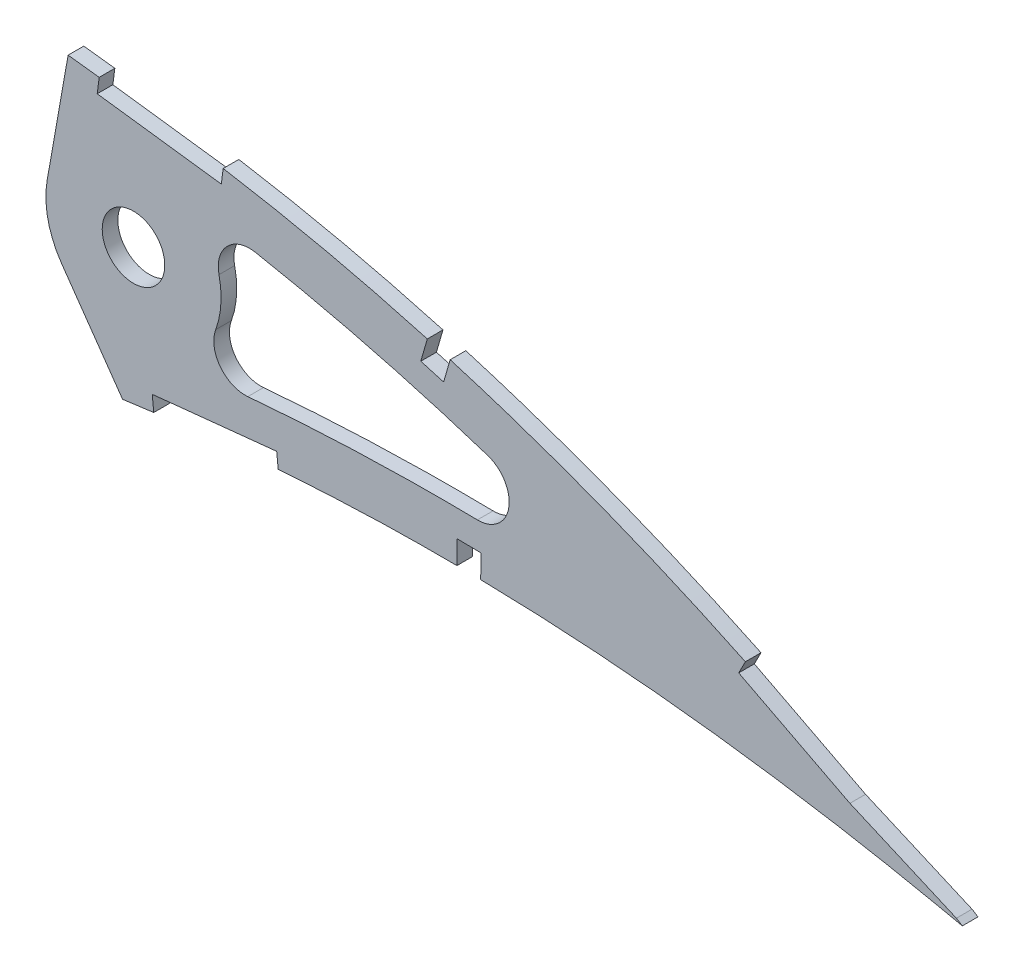
SolidWorks part; units mm, degrees
material "Plywood"
ref_plane "Front Plane" through (0, 0, 0) normal (0, 0, 1) x (1, 0, 0)
ref_plane "Top Plane" through (0, 0, 0) normal (0, 1, 0) x (1, 0, 0)
ref_plane "Right Plane" through (0, 0, 0) normal (1, 0, 0) x (0, 0, -1)
curve "Curve1"
  spline degree 3 poles (554.3197, 0.8642, 0) (554.2772, 0.8904, 0) (554.1075, 0.9953, 0) (553.7252, 1.2298, 0) (553.0885, 1.6204, 0) (552.1972, 2.1644, 0) (551.0519, 2.8603, 0) (549.6522, 3.7033, 0) (547.9988, 4.6906, 0) (546.0922, 5.8176, 0) (543.9326, 7.0789, 0) (541.5207, 8.4695, 0) (538.8569, 9.9815, 0) (535.942, 11.6087, 0) (532.7772, 13.3434, 0) (529.3631, 15.1777, 0) (525.7007, 17.1023, 0) (521.7917, 19.109, 0) (517.6366, 21.1866, 0) (513.2374, 23.3265, 0) (508.5956, 25.518, 0) (503.7128, 27.7495, 0) (498.5918, 30.0118, 0) (493.234, 32.2909, 0) (487.6424, 34.577, 0) (481.8195, 36.8569, 0) (475.7686, 39.1203, 0) (469.4922, 41.3526, 0) (462.9949, 43.5439, 0) (456.2798, 45.6802, 0) (449.3518, 47.7496, 0) (442.2149, 49.739, 0) (434.875, 51.6379, 0) (427.3368, 53.4327, 0) (419.6066, 55.1112, 0) (411.6907, 56.6635, 0) (403.5957, 58.0739, 0) (395.344, 59.3415, 0) (387.0683, 60.3958, 0) (378.8096, 61.4299, 0) (370.5633, 62.4014, 0) (362.2161, 63.3317, 0) (353.7762, 64.2156, 0) (345.252, 65.0503, 0) (336.6519, 65.8323, 0) (327.9851, 66.5592, 0) (319.2598, 67.227, 0) (310.4852, 67.8346, 0) (301.6702, 68.3766, 0) (292.8239, 68.8527, 0) (283.9555, 69.2595, 0) (275.0741, 69.5943, 0) (266.1892, 69.8549, 0) (257.3099, 70.039, 0) (248.446, 70.1454, 0) (239.6066, 70.171, 0) (230.8014, 70.1156, 0) (222.0395, 69.9772, 0) (213.3305, 69.7538, 0) (204.6838, 69.4452, 0) (196.1087, 69.0513, 0) (187.6145, 68.5689, 0) (179.2105, 68.0012, 0) (170.9059, 67.3456, 0) (162.7101, 66.6021, 0) (154.6315, 65.7736, 0) (146.6791, 64.8581, 0) (138.8614, 63.858, 0) (131.1871, 62.7754, 0) (123.6647, 61.6096, 0) (116.3022, 60.3641, 0) (109.1077, 59.04, 0) (102.0887, 57.6413, 0) (95.2529, 56.1683, 0) (88.6074, 54.6255, 0) (82.1593, 53.0155, 0) (75.9155, 51.3413, 0) (69.8822, 49.607, 0) (64.0656, 47.8163, 0) (58.4725, 45.9714, 0) (53.107, 44.0792, 0) (47.9758, 42.141, 0) (43.0829, 40.1629, 0) (38.4338, 38.1474, 0) (34.0322, 36.1008, 0) (29.883, 34.0255, 0) (25.9891, 31.9271, 0) (22.3545, 29.809, 0) (18.9827, 27.675, 0) (15.875, 25.5306, 0) (13.0358, 23.3771, 0) (10.4661, 21.22, 0) (8.1674, 19.0625, 0) (6.143, 16.9061, 0) (4.3929, 14.7547, 0) (2.9194, 12.6099, 0) (1.7228, 10.4738, 0) (0.8056, 8.3479, 0) (0.1671, 6.2334, 0) (-0.1824, 4.1334, 0) (-0.2694, 2.0463, 0) (-0.0897, 0.6811, 0) (0, 0, 0) knots 0 0 0 0 0.000254 0.001015 0.002283 0.004057 0.006331 0.009105 0.012374 0.016134 0.02038 0.025106 0.030306 0.035972 0.0421 0.048678 0.055702 0.06316 0.071046 0.07935 0.088063 0.097176 0.106678 0.116562 0.126814 0.137428 0.148394 0.1597 0.171338 0.183298 0.19557 0.208144 0.221012 0.234162 0.247587 0.261277 0.275223 0.289414 0.303771 0.317689 0.331784 0.34604 0.360444 0.374983 0.38964 0.404403 0.419257 0.434187 0.449177 0.464215 0.479284 0.49437 0.509458 0.524532 0.539579 0.554583 0.56953 0.584403 0.599191 0.613877 0.628447 0.642889 0.657186 0.671326 0.685294 0.699078 0.712665 0.726043 0.739198 0.752118 0.764792 0.777208 0.789356 0.801224 0.812804 0.824083 0.835055 0.84571 0.856038 0.866034 0.875689 0.884998 0.893953 0.902553 0.910789 0.918661 0.926166 0.933303 0.940071 0.946475 0.952518 0.958205 0.963547 0.968557 0.97325 0.977651 0.981787 0.985694 0.989415 0.993001 0.996508 1 1 1 1
curve "Curve2"
  spline degree 3 poles (0, 0, 0) (0.1423, -0.672, 0) (0.4277, -2.019, 0) (1.203, -3.9582, 0) (2.2282, -5.8223, 0) (3.5249, -7.6064, 0) (5.0845, -9.31, 0) (6.9036, -10.9348, 0) (8.9803, -12.4801, 0) (11.3119, -13.945, 0) (13.8951, -15.3312, 0) (16.7269, -16.6378, 0) (19.8048, -17.8643, 0) (23.1254, -19.0092, 0) (26.6846, -20.0741, 0) (30.4791, -21.0566, 0) (34.5045, -21.9578, 0) (38.7571, -22.7757, 0) (43.232, -23.5109, 0) (47.9248, -24.1631, 0) (52.8305, -24.7327, 0) (57.9444, -25.2185, 0) (63.2614, -25.6215, 0) (68.7762, -25.942, 0) (74.4834, -26.1811, 0) (80.3777, -26.3377, 0) (86.4531, -26.4144, 0) (92.7043, -26.4123, 0) (99.1251, -26.3308, 0) (105.71, -26.1745, 0) (112.4527, -25.9423, 0) (119.3471, -25.6371, 0) (126.387, -25.2619, 0) (133.5661, -24.818, 0) (140.8781, -24.3074, 0) (148.3166, -23.7341, 0) (155.8748, -23.0997, 0) (163.5462, -22.4077, 0) (171.324, -21.6617, 0) (179.2015, -20.864, 0) (187.1716, -20.0183, 0) (195.2274, -19.1275, 0) (203.3619, -18.1963, 0) (211.5677, -17.2262, 0) (219.8379, -16.223, 0) (228.1647, -15.1885, 0) (236.5412, -14.1266, 0) (244.9597, -13.0425, 0) (253.4125, -11.9359, 0) (261.8924, -10.8148, 0) (270.3912, -9.6781, 0) (278.9016, -8.5319, 0) (287.4156, -7.3796, 0) (295.925, -6.2216, 0) (304.4222, -5.0626, 0) (312.8995, -3.9059, 0) (321.3485, -2.7516, 0) (329.7616, -1.6054, 0) (338.1302, -0.4672, 0) (346.4467, 0.6607, 0) (354.7031, 1.775, 0) (362.8916, 2.8743, 0) (371.0037, 3.9578, 0) (379.0314, 5.0259, 0) (386.8463, 6.0463, 0) (394.4281, 7.0733, 0) (401.8022, 7.9152, 0) (409.0845, 8.6338, 0) (416.2825, 9.2229, 0) (423.3877, 9.6911, 0) (430.3918, 10.0417, 0) (437.2865, 10.2795, 0) (444.0631, 10.4116, 0) (450.7132, 10.4414, 0) (457.2276, 10.3785, 0) (463.598, 10.2277, 0) (469.8153, 9.9961, 0) (475.8709, 9.6912, 0) (481.7563, 9.3216, 0) (487.4626, 8.8925, 0) (492.9818, 8.4141, 0) (498.3055, 7.8933, 0) (503.4254, 7.336, 0) (508.334, 6.7541, 0) (513.0236, 6.1512, 0) (517.4871, 5.5374, 0) (521.7172, 4.9187, 0) (525.7074, 4.3032, 0) (529.4512, 3.6966, 0) (532.9427, 3.1071, 0) (536.1764, 2.5402, 0) (539.1467, 2.0013, 0) (541.8495, 1.4973, 0) (544.2794, 1.0307, 0) (546.4331, 0.6092, 0) (548.3068, 0.2346, 0) (549.8976, -0.0878, 0) (551.2027, -0.3567, 0) (552.2202, -0.5677, 0) (552.948, -0.7211, 0) (553.3854, -0.8124, 0) (553.5798, -0.8538, 0) (553.6283, -0.8642, 0) knots 0 0 0 0 0.003638 0.007293 0.011028 0.014901 0.018963 0.023258 0.027821 0.032679 0.037853 0.043362 0.049215 0.055422 0.061989 0.068918 0.076211 0.083868 0.091887 0.100266 0.109 0.118085 0.127515 0.137285 0.147388 0.157816 0.168563 0.179619 0.190977 0.202627 0.21456 0.226767 0.239236 0.251959 0.264924 0.27812 0.291536 0.30516 0.318981 0.332985 0.347163 0.361499 0.375981 0.390597 0.405333 0.420175 0.43511 0.450124 0.465203 0.480333 0.495501 0.51069 0.525887 0.541078 0.556247 0.571382 0.586466 0.601485 0.616424 0.631269 0.646007 0.660621 0.675098 0.689423 0.703582 0.716908 0.730009 0.742952 0.755726 0.76832 0.780724 0.792927 0.804916 0.816679 0.828204 0.839475 0.850481 0.861208 0.871639 0.881763 0.891564 0.901027 0.910139 0.918884 0.927249 0.935221 0.942785 0.949928 0.956638 0.962904 0.968712 0.974054 0.978918 0.983297 0.98718 0.990561 0.993433 0.995791 0.99763 0.998946 0.999737 1 1 1 1
sketch "Sketch1" plane through (0, 0, 0) normal (0, 0, 1) x (1, 0, 0)
  line L28 (0, 63.5) -> (-23.1981, 63.5) construction
  line L39 (379.9183, -27.3345) -> (379.9183, 27.3345) construction
  line L40 (368.4067, 59.4277) -> (353.2793, 2.9714) construction
  line L41 (537.5238, 0.838) -> (542.0214, -1.9404)
  line L42 (536.8534, -0.838) -> (542.0214, -1.9404)
  circle A0 centre (68.58, 6.35) radius 9.525 construction
  circle A1 centre (246.38, 6.35) radius 9.525 construction
  spline S3 degree 3 poles (0, 0) (0.138, -0.6516) (0.4147, -1.9578) (1.1665, -3.8383) (2.1607, -5.6459) (3.4181, -7.3759) (4.9305, -9.0279) (6.6944, -10.6035) (8.7082, -12.1019) (10.9692, -13.5225) (13.4741, -14.8667) (16.2201, -16.1336) (19.2047, -17.323) (22.4247, -18.4332) (25.8761, -19.4659) (29.5556, -20.4185) (33.4591, -21.2925) (37.5827, -22.0856) (41.9221, -22.7985) (46.4726, -23.431) (51.2297, -23.9833) (56.1887, -24.4544) (61.3446, -24.8452) (66.6923, -25.156) (72.2266, -25.3878) (77.9422, -25.5397) (83.8336, -25.6141) (89.8954, -25.612) (96.1216, -25.533) (102.507, -25.3814) (109.0454, -25.1563) (115.7309, -24.8603) (122.5575, -24.4965) (129.5191, -24.066) (136.6095, -23.5709) (143.8226, -23.015) (151.1518, -22.3997) (158.5908, -21.7287) (166.1329, -21.0053) (173.7717, -20.2318) (181.5003, -19.4118) (189.312, -18.5479) (197.2, -17.6449) (205.1572, -16.7043) (213.1768, -15.7315) (221.2513, -14.7283) (229.374, -13.6986) (237.5374, -12.6473) (245.7341, -11.5743) (253.957, -10.4871) (262.1983, -9.3849) (270.4508, -8.2734) (278.7069, -7.156) (286.9584, -6.033) (295.1983, -4.9092) (303.4187, -3.7876) (311.6117, -2.6683) (319.7698, -1.5568) (327.8848, -0.4531) (335.9493, 0.6407) (343.9556, 1.7212) (351.896, 2.7872) (359.7623, 3.8379) (367.5468, 4.8736) (375.1249, 5.8631) (382.4769, 6.859) (389.6276, 7.6754) (396.6892, 8.3722) (403.6691, 8.9435) (410.559, 9.3975) (417.3509, 9.7374) (424.0367, 9.968) (430.608, 10.0961) (437.0566, 10.1251) (443.3736, 10.064) (449.5509, 9.9178) (455.5799, 9.6932) (461.4521, 9.3976) (467.1591, 9.0391) (472.6925, 8.6231) (478.0445, 8.1591) (483.2068, 7.6541) (488.1716, 7.1138) (492.9315, 6.5494) (497.479, 5.9648) (501.8072, 5.3696) (505.9092, 4.7697) (509.7784, 4.1728) (513.4088, 3.5846) (516.7946, 3.013) (519.9303, 2.4632) (522.8106, 1.9407) (525.4315, 1.4519) (527.7877, 0.9995) (529.8762, 0.5907) (531.6931, 0.2275) (533.2357, -0.0851) (534.5012, -0.3459) (535.4879, -0.5505) (536.1937, -0.6992) (536.6178, -0.7878) (536.8063, -0.828) (536.8534, -0.838) knots 0 0 0 0 0.003638 0.007293 0.011028 0.014901 0.018963 0.023258 0.027821 0.032679 0.037853 0.043362 0.049215 0.055422 0.061989 0.068918 0.076211 0.083868 0.091887 0.100266 0.109 0.118085 0.127515 0.137285 0.147388 0.157816 0.168563 0.179619 0.190977 0.202627 0.21456 0.226767 0.239236 0.251959 0.264924 0.27812 0.291536 0.30516 0.318981 0.332985 0.347163 0.361499 0.375981 0.390597 0.405333 0.420175 0.43511 0.450124 0.465203 0.480333 0.495501 0.51069 0.525887 0.541078 0.556247 0.571382 0.586466 0.601485 0.616424 0.631269 0.646007 0.660621 0.675098 0.689423 0.703582 0.716908 0.730009 0.742952 0.755726 0.76832 0.780724 0.792927 0.804916 0.816679 0.828204 0.839475 0.850481 0.861208 0.871639 0.881763 0.891564 0.901027 0.910139 0.918884 0.927249 0.935221 0.942785 0.949928 0.956638 0.962904 0.968712 0.974054 0.978918 0.983297 0.98718 0.990561 0.993433 0.995791 0.99763 0.998946 0.999737 1 1 1 1
  spline S6 degree 3 poles (537.5238, 0.838) (537.4826, 0.8635) (537.3181, 0.9651) (536.9473, 1.1925) (536.3299, 1.5713) (535.4656, 2.0988) (534.3551, 2.7737) (532.9977, 3.5911) (531.3944, 4.5485) (529.5456, 5.6413) (527.4514, 6.8644) (525.1126, 8.2129) (522.5295, 9.6791) (519.703, 11.2569) (516.6341, 12.9391) (513.3234, 14.7178) (509.772, 16.5841) (505.9814, 18.53) (501.9522, 20.5446) (497.6863, 22.6197) (493.1852, 24.7448) (488.4503, 26.9087) (483.4845, 29.1025) (478.289, 31.3125) (472.8669, 33.5293) (467.2204, 35.7401) (461.3528, 37.9349) (455.2666, 40.0996) (448.9661, 42.2246) (442.4545, 44.296) (435.7364, 46.3028) (428.8157, 48.2319) (421.6983, 50.0733) (414.3885, 51.8137) (406.8926, 53.4414) (399.2165, 54.9466) (391.3668, 56.3143) (383.365, 57.5434) (375.3401, 58.5658) (367.3317, 59.5686) (359.3352, 60.5106) (351.241, 61.4127) (343.0568, 62.2698) (334.7908, 63.0793) (326.4514, 63.8376) (318.0471, 64.5425) (309.5862, 65.19) (301.0775, 65.7792) (292.5296, 66.3048) (283.9513, 66.7665) (275.3516, 67.161) (266.7393, 67.4856) (258.1236, 67.7383) (249.5134, 67.9168) (240.9181, 68.0199) (232.3465, 68.0449) (223.8081, 67.9911) (215.3117, 67.8569) (206.8666, 67.6403) (198.4819, 67.341) (190.1666, 66.959) (181.9298, 66.4913) (173.7804, 65.9407) (165.7275, 65.305) (157.78, 64.584) (149.9461, 63.7807) (142.2347, 62.8929) (134.6539, 61.9231) (127.2121, 60.8733) (119.9176, 59.7429) (112.7783, 58.535) (105.8017, 57.2511) (98.9954, 55.8947) (92.3667, 54.4664) (85.9226, 52.9703) (79.6699, 51.4091) (73.6153, 49.7857) (67.7648, 48.1039) (62.1244, 46.3675) (56.7008, 44.5785) (51.4979, 42.7436) (46.5222, 40.8641) (41.7775, 38.9459) (37.2693, 36.9916) (33.0011, 35.007) (28.9776, 32.9945) (25.2017, 30.9597) (21.6772, 28.9058) (18.4075, 26.8364) (15.394, 24.757) (12.6408, 22.6688) (10.1489, 20.577) (7.9199, 18.4849) (5.9569, 16.3939) (4.2598, 14.3076) (2.831, 12.2278) (1.6706, 10.1565) (0.7812, 8.095) (0.162, 6.0445) (-0.1769, 4.0082) (-0.2612, 1.9843) (-0.087, 0.6604) (0, 0) knots 0 0 0 0 0.000254 0.001015 0.002283 0.004057 0.006331 0.009105 0.012374 0.016134 0.02038 0.025106 0.030306 0.035972 0.0421 0.048678 0.055702 0.06316 0.071046 0.07935 0.088063 0.097176 0.106678 0.116562 0.126814 0.137428 0.148394 0.1597 0.171338 0.183298 0.19557 0.208144 0.221012 0.234162 0.247587 0.261277 0.275223 0.289414 0.303771 0.317689 0.331784 0.34604 0.360444 0.374983 0.38964 0.404403 0.419257 0.434187 0.449177 0.464215 0.479284 0.49437 0.509458 0.524532 0.539579 0.554583 0.56953 0.584403 0.599191 0.613877 0.628447 0.642889 0.657186 0.671326 0.685294 0.699078 0.712665 0.726043 0.739198 0.752118 0.764792 0.777208 0.789356 0.801224 0.812804 0.824083 0.835055 0.84571 0.856038 0.866034 0.875689 0.884998 0.893953 0.902553 0.910789 0.918661 0.926166 0.933303 0.940071 0.946475 0.952518 0.958205 0.963547 0.968557 0.97325 0.977651 0.981787 0.985694 0.989415 0.993001 0.996508 1 1 1 1
  point P10 (78.5929, 16.5948)
  point P11 (227.8303, 32.4941)
  dimension "D2" = 19.05
  dimension "D18" = 177.8
  dimension "D3" = 15
  dimension "D5" = 63.5
  dimension "D7" = 57.15
  dimension "D12" = 57.15
  dimension "D17" = 68.58
extrude "Boss-Extrude1" add sketch "Sketch1" along normal blind 3.175
sketch "Sketch4" plane through (0, 0, 0) normal (0, 0, -1) x (-1, 0, 0)
  line L0 (-356.287, 36.32) -> (-360.5267, 60.365)
  line L1 (-359.2323, 23.0344) -> (-371.5795, 5.4008)
  line L2 (-373.7968, 33.2326) -> (-412.6852, 33.2326)
  circle A0 centre (-373.7968, 33.2326) radius 17.78
  circle A1 centre (-373.7968, 33.2326) radius 6.35
  spline S0 degree 3 poles (-1632.0302, 1674.0962) (-565.4284, -22.6918) (-552.7247, -8.4851) (-536.9473, 1.1925) (-536.3299, 1.5713) (-535.4656, 2.0988) (-534.3551, 2.7737) (-532.9977, 3.5911) (-531.3944, 4.5485) (-529.5456, 5.6413) (-527.4514, 6.8644) (-525.1126, 8.2129) (-522.5295, 9.6791) (-519.703, 11.2569) (-516.6341, 12.9391) (-513.3234, 14.7178) (-509.772, 16.5841) (-505.9814, 18.53) (-501.9522, 20.5446) (-497.6863, 22.6197) (-493.1852, 24.7448) (-488.4503, 26.9087) (-483.4845, 29.1025) (-478.289, 31.3125) (-472.8669, 33.5293) (-467.2204, 35.7401) (-461.3528, 37.9349) (-455.2666, 40.0996) (-448.9661, 42.2246) (-442.4545, 44.296) (-435.7364, 46.3028) (-428.8157, 48.2319) (-421.6983, 50.0733) (-414.3885, 51.8137) (-406.8926, 53.4414) (-399.2165, 54.9466) (-391.3668, 56.3143) (-383.365, 57.5434) (-375.3401, 58.5658) (-367.3317, 59.5686) (-359.3352, 60.5106) (-351.241, 61.4127) (-343.0568, 62.2698) (-334.7908, 63.0793) (-326.4514, 63.8376) (-318.0471, 64.5425) (-309.5862, 65.19) (-301.0775, 65.7792) (-292.5296, 66.3048) (-283.9513, 66.7665) (-275.3516, 67.161) (-266.7393, 67.4856) (-258.1236, 67.7383) (-249.5134, 67.9168) (-240.9181, 68.0199) (-232.3465, 68.0449) (-223.8081, 67.9911) (-215.3117, 67.8569) (-206.8666, 67.6403) (-198.4819, 67.341) (-190.1666, 66.959) (-181.9298, 66.4913) (-173.7804, 65.9407) (-165.7275, 65.305) (-157.78, 64.584) (-149.9461, 63.7807) (-142.2347, 62.8929) (-134.6539, 61.9231) (-127.2121, 60.8733) (-119.9176, 59.7429) (-112.7783, 58.535) (-105.8017, 57.2511) (-98.9954, 55.8947) (-92.3667, 54.4664) (-85.9226, 52.9703) (-79.6699, 51.4091) (-73.6153, 49.7857) (-67.7648, 48.1039) (-62.1244, 46.3675) (-56.7008, 44.5785) (-51.4979, 42.7436) (-46.5222, 40.8641) (-41.7775, 38.9459) (-37.2693, 36.9916) (-33.0011, 35.007) (-28.9776, 32.9945) (-25.2017, 30.9597) (-21.6772, 28.9058) (-18.4075, 26.8364) (-15.394, 24.757) (-12.6408, 22.6688) (-10.1489, 20.577) (-7.9199, 18.4849) (-5.9569, 16.3939) (-4.2598, 14.3076) (-2.831, 12.2278) (-1.6706, 10.1565) (-0.7812, 8.095) (-0.162, 6.0445) (0.1769, 4.0082) (1.1707, -19.8347) (-66.7598, -38.6935) (1990.434, -189.4699) knots -0.094882 -0.094882 -0.094882 -0.094882 0.000254 0.001015 0.002283 0.004057 0.006331 0.009105 0.012374 0.016134 0.02038 0.025106 0.030306 0.035972 0.0421 0.048678 0.055702 0.06316 0.071046 0.07935 0.088063 0.097176 0.106678 0.116562 0.126814 0.137428 0.148394 0.1597 0.171338 0.183298 0.19557 0.208144 0.221012 0.234162 0.247587 0.261277 0.275223 0.289414 0.303771 0.317689 0.331784 0.34604 0.360444 0.374983 0.38964 0.404403 0.419257 0.434187 0.449177 0.464215 0.479284 0.49437 0.509458 0.524532 0.539579 0.554583 0.56953 0.584403 0.599191 0.613877 0.628447 0.642889 0.657186 0.671326 0.685294 0.699078 0.712665 0.726043 0.739198 0.752118 0.764792 0.777208 0.789356 0.801224 0.812804 0.824083 0.835055 0.84571 0.856038 0.866034 0.875689 0.884998 0.893953 0.902553 0.910789 0.918661 0.926166 0.933303 0.940071 0.946475 0.952518 0.958205 0.963547 0.968557 0.97325 0.977651 0.981787 0.985694 0.989415 0.993001 0.996508 1.114113 1.114113 1.114113 1.114113 only from (-537.5238, 0.838) to (0, 0) construction
  spline S1 degree 3 poles (1940.1203, -483.4322) (-49.9299, 58.7424) (7.7069, 18.357) (-1.1665, -3.8383) (-2.1607, -5.6459) (-3.4181, -7.3759) (-4.9305, -9.0279) (-6.6944, -10.6035) (-8.7082, -12.1019) (-10.9692, -13.5225) (-13.4741, -14.8667) (-16.2201, -16.1336) (-19.2047, -17.323) (-22.4247, -18.4332) (-25.8761, -19.4659) (-29.5556, -20.4185) (-33.4591, -21.2925) (-37.5827, -22.0856) (-41.9221, -22.7985) (-46.4726, -23.431) (-51.2297, -23.9833) (-56.1887, -24.4544) (-61.3446, -24.8452) (-66.6923, -25.156) (-72.2266, -25.3878) (-77.9422, -25.5397) (-83.8336, -25.6141) (-89.8954, -25.612) (-96.1216, -25.533) (-102.507, -25.3814) (-109.0454, -25.1563) (-115.7309, -24.8603) (-122.5575, -24.4965) (-129.5191, -24.066) (-136.6095, -23.5709) (-143.8226, -23.015) (-151.1518, -22.3997) (-158.5908, -21.7287) (-166.1329, -21.0053) (-173.7717, -20.2318) (-181.5003, -19.4118) (-189.312, -18.5479) (-197.2, -17.6449) (-205.1572, -16.7043) (-213.1768, -15.7315) (-221.2513, -14.7283) (-229.374, -13.6986) (-237.5374, -12.6473) (-245.7341, -11.5743) (-253.957, -10.4871) (-262.1983, -9.3849) (-270.4508, -8.2734) (-278.7069, -7.156) (-286.9584, -6.033) (-295.1983, -4.9092) (-303.4187, -3.7876) (-311.6117, -2.6683) (-319.7698, -1.5568) (-327.8848, -0.4531) (-335.9493, 0.6407) (-343.9556, 1.7212) (-351.896, 2.7872) (-359.7623, 3.8379) (-367.5468, 4.8736) (-375.1249, 5.8631) (-382.4769, 6.859) (-389.6276, 7.6754) (-396.6892, 8.3722) (-403.6691, 8.9435) (-410.559, 9.3975) (-417.3509, 9.7374) (-424.0367, 9.968) (-430.608, 10.0961) (-437.0566, 10.1251) (-443.3736, 10.064) (-449.5509, 9.9178) (-455.5799, 9.6932) (-461.4521, 9.3976) (-467.1591, 9.0391) (-472.6925, 8.6231) (-478.0445, 8.1591) (-483.2068, 7.6541) (-488.1716, 7.1138) (-492.9315, 6.5494) (-497.479, 5.9648) (-501.8072, 5.3696) (-505.9092, 4.7697) (-509.7784, 4.1728) (-513.4088, 3.5846) (-516.7946, 3.013) (-519.9303, 2.4632) (-522.8106, 1.9407) (-525.4315, 1.4519) (-527.7877, 0.9995) (-529.8762, 0.5907) (-531.6931, 0.2275) (-533.2357, -0.0851) (-534.5012, -0.3459) (-535.4879, -0.5505) (-536.1937, -0.6992) (-552.4366, -4.0895) (-567.1821, -13.3973) (-997.8539, 1944.6618) knots -0.119141 -0.119141 -0.119141 -0.119141 0.003638 0.007293 0.011028 0.014901 0.018963 0.023258 0.027821 0.032679 0.037853 0.043362 0.049215 0.055422 0.061989 0.068918 0.076211 0.083868 0.091887 0.100266 0.109 0.118085 0.127515 0.137285 0.147388 0.157816 0.168563 0.179619 0.190977 0.202627 0.21456 0.226767 0.239236 0.251959 0.264924 0.27812 0.291536 0.30516 0.318981 0.332985 0.347163 0.361499 0.375981 0.390597 0.405333 0.420175 0.43511 0.450124 0.465203 0.480333 0.495501 0.51069 0.525887 0.541078 0.556247 0.571382 0.586466 0.601485 0.616424 0.631269 0.646007 0.660621 0.675098 0.689423 0.703582 0.716908 0.730009 0.742952 0.755726 0.76832 0.780724 0.792927 0.804916 0.816679 0.828204 0.839475 0.850481 0.861208 0.871639 0.881763 0.891564 0.901027 0.910139 0.918884 0.927249 0.935221 0.942785 0.949928 0.956638 0.962904 0.968712 0.974054 0.978918 0.983297 0.98718 0.990561 0.993433 0.995791 0.99763 0.998946 0.999737 1.088404 1.088404 1.088404 1.088404 only from (0, 0) to (-536.8534, -0.838) construction
  spline S2 degree 3 poles (-537.5238, 0.838) (-537.4826, 0.8635) (-537.3181, 0.9651) (-536.9473, 1.1925) (-536.3299, 1.5713) (-535.4656, 2.0988) (-534.3551, 2.7737) (-532.9977, 3.5911) (-531.3944, 4.5485) (-529.5456, 5.6413) (-527.4514, 6.8644) (-525.1126, 8.2129) (-522.5295, 9.6791) (-519.703, 11.2569) (-516.6341, 12.9391) (-513.3234, 14.7178) (-509.772, 16.5841) (-505.9814, 18.53) (-501.9522, 20.5446) (-497.6863, 22.6197) (-493.1852, 24.7448) (-488.4503, 26.9087) (-483.4845, 29.1025) (-478.289, 31.3125) (-472.8669, 33.5293) (-467.2204, 35.7401) (-461.3528, 37.9349) (-455.2666, 40.0996) (-448.9661, 42.2246) (-442.4545, 44.296) (-435.7364, 46.3028) (-428.8157, 48.2319) (-421.6983, 50.0733) (-414.3885, 51.8137) (-406.8926, 53.4414) (-399.2165, 54.9466) (-391.3668, 56.3143) (-383.365, 57.5434) (-375.3401, 58.5658) (-367.3317, 59.5686) (-359.3352, 60.5106) (-351.241, 61.4127) (-343.0568, 62.2698) (-334.7908, 63.0793) (-326.4514, 63.8376) (-318.0471, 64.5425) (-309.5862, 65.19) (-301.0775, 65.7792) (-292.5296, 66.3048) (-283.9513, 66.7665) (-275.3516, 67.161) (-266.7393, 67.4856) (-258.1236, 67.7383) (-249.5134, 67.9168) (-240.9181, 68.0199) (-232.3465, 68.0449) (-223.8081, 67.9911) (-215.3117, 67.8569) (-206.8666, 67.6403) (-198.4819, 67.341) (-190.1666, 66.959) (-181.9298, 66.4913) (-173.7804, 65.9407) (-165.7275, 65.305) (-157.78, 64.584) (-149.9461, 63.7807) (-142.2347, 62.8929) (-134.6539, 61.9231) (-127.2121, 60.8733) (-119.9176, 59.7429) (-112.7783, 58.535) (-105.8017, 57.2511) (-98.9954, 55.8947) (-92.3667, 54.4664) (-85.9226, 52.9703) (-79.6699, 51.4091) (-73.6153, 49.7857) (-67.7648, 48.1039) (-62.1244, 46.3675) (-56.7008, 44.5785) (-51.4979, 42.7436) (-46.5222, 40.8641) (-41.7775, 38.9459) (-37.2693, 36.9916) (-33.0011, 35.007) (-28.9776, 32.9945) (-25.2017, 30.9597) (-21.6772, 28.9058) (-18.4075, 26.8364) (-15.394, 24.757) (-12.6408, 22.6688) (-10.1489, 20.577) (-7.9199, 18.4849) (-5.9569, 16.3939) (-4.2598, 14.3076) (-2.831, 12.2278) (-1.6706, 10.1565) (-0.7812, 8.095) (-0.162, 6.0445) (0.1769, 4.0082) (0.2612, 1.9843) (0.087, 0.6604) (0, 0) knots 0 0 0 0 0.000254 0.001015 0.002283 0.004057 0.006331 0.009105 0.012374 0.016134 0.02038 0.025106 0.030306 0.035972 0.0421 0.048678 0.055702 0.06316 0.071046 0.07935 0.088063 0.097176 0.106678 0.116562 0.126814 0.137428 0.148394 0.1597 0.171338 0.183298 0.19557 0.208144 0.221012 0.234162 0.247587 0.261277 0.275223 0.289414 0.303771 0.317689 0.331784 0.34604 0.360444 0.374983 0.38964 0.404403 0.419257 0.434187 0.449177 0.464215 0.479284 0.49437 0.509458 0.524532 0.539579 0.554583 0.56953 0.584403 0.599191 0.613877 0.628447 0.642889 0.657186 0.671326 0.685294 0.699078 0.712665 0.726043 0.739198 0.752118 0.764792 0.777208 0.789356 0.801224 0.812804 0.824083 0.835055 0.84571 0.856038 0.866034 0.875689 0.884998 0.893953 0.902553 0.910789 0.918661 0.926166 0.933303 0.940071 0.946475 0.952518 0.958205 0.963547 0.968557 0.97325 0.977651 0.981787 0.985694 0.989415 0.993001 0.996508 1 1 1 1
  spline S3 degree 3 poles (0, 0) (-0.138, -0.6516) (-0.4147, -1.9578) (-1.1665, -3.8383) (-2.1607, -5.6459) (-3.4181, -7.3759) (-4.9305, -9.0279) (-6.6944, -10.6035) (-8.7082, -12.1019) (-10.9692, -13.5225) (-13.4741, -14.8667) (-16.2201, -16.1336) (-19.2047, -17.323) (-22.4247, -18.4332) (-25.8761, -19.4659) (-29.5556, -20.4185) (-33.4591, -21.2925) (-37.5827, -22.0856) (-41.9221, -22.7985) (-46.4726, -23.431) (-51.2297, -23.9833) (-56.1887, -24.4544) (-61.3446, -24.8452) (-66.6923, -25.156) (-72.2266, -25.3878) (-77.9422, -25.5397) (-83.8336, -25.6141) (-89.8954, -25.612) (-96.1216, -25.533) (-102.507, -25.3814) (-109.0454, -25.1563) (-115.7309, -24.8603) (-122.5575, -24.4965) (-129.5191, -24.066) (-136.6095, -23.5709) (-143.8226, -23.015) (-151.1518, -22.3997) (-158.5908, -21.7287) (-166.1329, -21.0053) (-173.7717, -20.2318) (-181.5003, -19.4118) (-189.312, -18.5479) (-197.2, -17.6449) (-205.1572, -16.7043) (-213.1768, -15.7315) (-221.2513, -14.7283) (-229.374, -13.6986) (-237.5374, -12.6473) (-245.7341, -11.5743) (-253.957, -10.4871) (-262.1983, -9.3849) (-270.4508, -8.2734) (-278.7069, -7.156) (-286.9584, -6.033) (-295.1983, -4.9092) (-303.4187, -3.7876) (-311.6117, -2.6683) (-319.7698, -1.5568) (-327.8848, -0.4531) (-335.9493, 0.6407) (-343.9556, 1.7212) (-351.896, 2.7872) (-359.7623, 3.8379) (-367.5468, 4.8736) (-375.1249, 5.8631) (-382.4769, 6.859) (-389.6276, 7.6754) (-396.6892, 8.3722) (-403.6691, 8.9435) (-410.559, 9.3975) (-417.3509, 9.7374) (-424.0367, 9.968) (-430.608, 10.0961) (-437.0566, 10.1251) (-443.3736, 10.064) (-449.5509, 9.9178) (-455.5799, 9.6932) (-461.4521, 9.3976) (-467.1591, 9.0391) (-472.6925, 8.6231) (-478.0445, 8.1591) (-483.2068, 7.6541) (-488.1716, 7.1138) (-492.9315, 6.5494) (-497.479, 5.9648) (-501.8072, 5.3696) (-505.9092, 4.7697) (-509.7784, 4.1728) (-513.4088, 3.5846) (-516.7946, 3.013) (-519.9303, 2.4632) (-522.8106, 1.9407) (-525.4315, 1.4519) (-527.7877, 0.9995) (-529.8762, 0.5907) (-531.6931, 0.2275) (-533.2357, -0.0851) (-534.5012, -0.3459) (-535.4879, -0.5505) (-536.1937, -0.6992) (-536.6178, -0.7878) (-536.8063, -0.828) (-536.8534, -0.838) knots 0 0 0 0 0.003638 0.007293 0.011028 0.014901 0.018963 0.023258 0.027821 0.032679 0.037853 0.043362 0.049215 0.055422 0.061989 0.068918 0.076211 0.083868 0.091887 0.100266 0.109 0.118085 0.127515 0.137285 0.147388 0.157816 0.168563 0.179619 0.190977 0.202627 0.21456 0.226767 0.239236 0.251959 0.264924 0.27812 0.291536 0.30516 0.318981 0.332985 0.347163 0.361499 0.375981 0.390597 0.405333 0.420175 0.43511 0.450124 0.465203 0.480333 0.495501 0.51069 0.525887 0.541078 0.556247 0.571382 0.586466 0.601485 0.616424 0.631269 0.646007 0.660621 0.675098 0.689423 0.703582 0.716908 0.730009 0.742952 0.755726 0.76832 0.780724 0.792927 0.804916 0.816679 0.828204 0.839475 0.850481 0.861208 0.871639 0.881763 0.891564 0.901027 0.910139 0.918884 0.927249 0.935221 0.942785 0.949928 0.956638 0.962904 0.968712 0.974054 0.978918 0.983297 0.98718 0.990561 0.993433 0.995791 0.99763 0.998946 0.999737 1 1 1 1
  spline S4 degree 1 poles (-532.1841, -7.8057) (-10.0219, 1.7185) knots 0 0 1 1 construction
  spline S5 degree 1 poles (-10.0219, 1.7185) (-538.9729, 9.0984) knots 0 0 1 1 construction
  spline S6 degree 3 poles (-532.1841, -7.8057) (-532.035, -7.7136) (-531.7436, -7.5345) (-531.1023, -7.1412) (-530.0303, -6.4862) (-527.85, -5.1645) (-523.4829, -2.5651) (-514.6678, 2.5066) (-496.7411, 12.095) (-470.3238, 24.1396) (-442.9694, 33.791) (-420.6386, 39.9785) (-406.5149, 43.1961) (-395.1531, 45.3637) (-386.5599, 46.8051) (-378.0384, 47.9972) (-369.1749, 49.1011) (-360.4166, 50.162) (-348.6799, 51.484) (-328.147, 53.5808) (-298.749, 55.9238) (-263.4315, 57.6196) (-228.1119, 58.0844) (-192.8506, 57.171) (-157.7356, 54.6709) (-128.7085, 51.0365) (-105.7459, 46.987) (-88.7097, 43.306) (-71.9299, 38.8842) (-58.261, 34.4734) (-47.6305, 30.4115) (-39.8596, 27.063) (-32.3674, 23.3733) (-25.2794, 19.2928) (-18.8179, 14.7781) (-14.319, 10.6534) (-11.7187, 7.3378) (-10.6606, 5.4268) (-10.2382, 4.2645) (-10.0884, 3.6968) (-10.0101, 3.295) (-9.9553, 2.8496) (-9.9432, 2.5723) (-9.9453, 2.4518) (-9.9493, 2.3713) (-9.9688, 2.1598) (-9.9949, 1.9339) (-10.0132, 1.7875) (-10.0219, 1.7185) knots 0 0 0 0 0.000976 0.001952 0.003903 0.007807 0.015613 0.031226 0.062452 0.124904 0.187357 0.218583 0.249809 0.265422 0.281035 0.296648 0.312261 0.327874 0.343487 0.374713 0.437166 0.499618 0.56207 0.624522 0.686974 0.749427 0.780653 0.811879 0.843105 0.874331 0.889944 0.905557 0.92117 0.936783 0.952396 0.968009 0.975816 0.983623 0.987526 0.989477 0.991429 0.993381 0.995332 0.996308 0.997284 0.99826 0.998748 0.999236 0.999236 0.999236 0.999236
  spline S7 degree 3 poles (-10.0219, 1.7185) (-10.0361, 1.6529) (-10.0665, 1.5144) (-10.1157, 1.2979) (-10.1669, 1.0931) (-10.1938, 1.0009) (-10.2267, 0.9008) (-10.3197, 0.6625) (-10.5705, 0.1458) (-10.9157, -0.4199) (-11.7404, -1.469) (-13.2635, -2.8937) (-16.5705, -5.1355) (-21.8641, -7.6046) (-29.0738, -9.8943) (-36.7462, -11.652) (-44.6834, -12.9788) (-52.7844, -13.9626) (-63.7273, -14.8945) (-77.583, -15.4719) (-94.3476, -15.4772) (-111.1866, -14.9569) (-133.6938, -13.7131) (-161.8825, -11.3422) (-195.7357, -7.6685) (-229.6092, -3.472) (-263.4966, 1.0208) (-297.4142, 5.6457) (-325.6956, 9.51) (-345.5133, 12.184) (-356.8358, 13.6973) (-363.916, 14.6412) (-369.594, 15.387) (-373.812, 15.9419) (-378.0525, 16.5127) (-382.4211, 17.0728) (-386.7861, 17.5755) (-392.5828, 18.1876) (-402.7738, 19.115) (-417.3468, 20.0031) (-440.7096, 20.5101) (-469.8877, 19.4483) (-498.8731, 16.2543) (-518.9745, 12.9996) (-528.9918, 11.1265) (-533.6061, 10.2081) (-535.7587, 9.7686) (-536.8071, 9.5524) (-537.7352, 9.359) (-538.3978, 9.2197) (-538.786, 9.1383) (-538.9729, 9.0984) knots 0.000796 0.000796 0.000796 0.000796 0.001284 0.001772 0.002748 0.003724 0.004699 0.006651 0.008603 0.012506 0.016409 0.024215 0.032021 0.047634 0.063247 0.078859 0.094472 0.110084 0.125697 0.156922 0.188147 0.219372 0.250597 0.313047 0.375498 0.437948 0.500398 0.562848 0.625299 0.656524 0.672136 0.687749 0.695555 0.703361 0.711168 0.718974 0.72678 0.734587 0.750199 0.781424 0.812649 0.8751 0.93755 0.968775 0.984387 0.992194 0.994145 0.996097 0.998048 0.999024 1 1 1 1
  spline M11 degree 3 poles (0, 0) (0.087, 0.6604) (0.2612, 1.9843) (0.1769, 4.0082) (-0.162, 6.0445) (-0.7812, 8.095) (-1.6706, 10.1565) (-2.831, 12.2278) (-4.2598, 14.3076) (-5.9569, 16.3939) (-7.9199, 18.4849) (-10.1489, 20.577) (-12.6408, 22.6688) (-15.394, 24.757) (-18.4075, 26.8364) (-21.6772, 28.9058) (-25.2017, 30.9597) (-28.9776, 32.9945) (-33.0011, 35.007) (-37.2693, 36.9916) (-41.7775, 38.9459) (-46.5222, 40.8641) (-51.4979, 42.7436) (-56.7008, 44.5785) (-62.1244, 46.3675) (-67.7648, 48.1039) (-73.6153, 49.7857) (-79.6699, 51.4091) (-85.9226, 52.9703) (-92.3667, 54.4664) (-98.9954, 55.8947) (-105.8017, 57.2511) (-112.7783, 58.535) (-119.9176, 59.7429) (-127.2121, 60.8733) (-134.6539, 61.9231) (-142.2347, 62.8929) (-149.9461, 63.7807) (-157.78, 64.584) (-165.7275, 65.305) (-173.7804, 65.9407) (-181.9298, 66.4913) (-190.1666, 66.959) (-198.4819, 67.341) (-206.8666, 67.6403) (-215.3117, 67.8569) (-223.8081, 67.9911) (-232.3465, 68.0449) (-240.9181, 68.0199) (-249.5134, 67.9168) (-258.1236, 67.7383) (-266.7393, 67.4856) (-275.3516, 67.161) (-283.9513, 66.7665) (-292.5296, 66.3048) (-301.0775, 65.7792) (-309.5862, 65.19) (-318.0471, 64.5425) (-326.4514, 63.8376) (-334.7908, 63.0793) (-343.0568, 62.2698) (-351.241, 61.4127) (-359.3352, 60.5106) (-367.3317, 59.5686) (-375.3401, 58.5658) (-383.365, 57.5434) (-391.3668, 56.3143) (-399.2165, 54.9466) (-406.8926, 53.4414) (-414.3885, 51.8137) (-421.6983, 50.0733) (-428.8157, 48.2319) (-435.7364, 46.3028) (-442.4545, 44.296) (-448.9661, 42.2246) (-455.2666, 40.0996) (-461.3528, 37.9349) (-467.2204, 35.7401) (-472.8669, 33.5293) (-478.289, 31.3125) (-483.4845, 29.1025) (-488.4503, 26.9087) (-493.1852, 24.7448) (-497.6863, 22.6197) (-501.9522, 20.5446) (-505.9814, 18.53) (-509.772, 16.5841) (-513.3234, 14.7178) (-516.6341, 12.9391) (-519.703, 11.2569) (-522.5295, 9.6791) (-525.1126, 8.2129) (-527.4514, 6.8644) (-529.5456, 5.6413) (-531.3944, 4.5485) (-532.9977, 3.5911) (-534.3551, 2.7737) (-535.4656, 2.0988) (-536.3299, 1.5713) (-536.9473, 1.1925) (-537.3181, 0.9651) (-537.4826, 0.8635) (-537.5238, 0.838) knots 0 0 0 0 0.003492 0.006999 0.010585 0.014306 0.018213 0.022349 0.02675 0.031443 0.036453 0.041795 0.047482 0.053525 0.059929 0.066697 0.073834 0.081339 0.089211 0.097447 0.106047 0.115002 0.124311 0.133966 0.143962 0.15429 0.164945 0.175917 0.187196 0.198776 0.210644 0.222792 0.235208 0.247882 0.260802 0.273957 0.287335 0.300922 0.314706 0.328674 0.342814 0.357111 0.371553 0.386123 0.400809 0.415597 0.43047 0.445417 0.460421 0.475468 0.490542 0.50563 0.520716 0.535785 0.550823 0.565813 0.580743 0.595597 0.61036 0.625017 0.639556 0.65396 0.668216 0.682311 0.696229 0.710586 0.724777 0.738723 0.752413 0.765838 0.778988 0.791856 0.80443 0.816702 0.828662 0.8403 0.851606 0.862572 0.873186 0.883438 0.893322 0.902824 0.911937 0.92065 0.928954 0.93684 0.944298 0.951322 0.9579 0.964028 0.969694 0.974894 0.97962 0.983866 0.987626 0.990895 0.993669 0.995943 0.997717 0.998985 0.999746 1 1 1 1
  spline M14 degree 3 poles (-536.8534, -0.838) (-536.8063, -0.828) (-536.6178, -0.7878) (-536.1937, -0.6992) (-535.4879, -0.5505) (-534.5012, -0.3459) (-533.2357, -0.0851) (-531.6931, 0.2275) (-529.8762, 0.5907) (-527.7877, 0.9995) (-525.4315, 1.4519) (-522.8106, 1.9407) (-519.9303, 2.4632) (-516.7946, 3.013) (-513.4088, 3.5846) (-509.7784, 4.1728) (-505.9092, 4.7697) (-501.8072, 5.3696) (-497.479, 5.9648) (-492.9315, 6.5494) (-488.1716, 7.1138) (-483.2068, 7.6541) (-478.0445, 8.1591) (-472.6925, 8.6231) (-467.1591, 9.0391) (-461.4521, 9.3976) (-455.5799, 9.6932) (-449.5509, 9.9178) (-443.3736, 10.064) (-437.0566, 10.1251) (-430.608, 10.0961) (-424.0367, 9.968) (-417.3509, 9.7374) (-410.559, 9.3975) (-403.6691, 8.9435) (-396.6892, 8.3722) (-389.6276, 7.6754) (-382.4769, 6.859) (-375.1249, 5.8631) (-367.5468, 4.8736) (-359.7623, 3.8379) (-351.896, 2.7872) (-343.9556, 1.7212) (-335.9493, 0.6407) (-327.8848, -0.4531) (-319.7698, -1.5568) (-311.6117, -2.6683) (-303.4187, -3.7876) (-295.1983, -4.9092) (-286.9584, -6.033) (-278.7069, -7.156) (-270.4508, -8.2734) (-262.1983, -9.3849) (-253.957, -10.4871) (-245.7341, -11.5743) (-237.5374, -12.6473) (-229.374, -13.6986) (-221.2513, -14.7283) (-213.1768, -15.7315) (-205.1572, -16.7043) (-197.2, -17.6449) (-189.312, -18.5479) (-181.5003, -19.4118) (-173.7717, -20.2318) (-166.1329, -21.0053) (-158.5908, -21.7287) (-151.1518, -22.3997) (-143.8226, -23.015) (-136.6095, -23.5709) (-129.5191, -24.066) (-122.5575, -24.4965) (-115.7309, -24.8603) (-109.0454, -25.1563) (-102.507, -25.3814) (-96.1216, -25.533) (-89.8954, -25.612) (-83.8336, -25.6141) (-77.9422, -25.5397) (-72.2266, -25.3878) (-66.6923, -25.156) (-61.3446, -24.8452) (-56.1887, -24.4544) (-51.2297, -23.9833) (-46.4726, -23.431) (-41.9221, -22.7985) (-37.5827, -22.0856) (-33.4591, -21.2925) (-29.5556, -20.4185) (-25.8761, -19.4659) (-22.4247, -18.4332) (-19.2047, -17.323) (-16.2201, -16.1336) (-13.4741, -14.8667) (-10.9692, -13.5225) (-8.7082, -12.1019) (-6.6944, -10.6035) (-4.9305, -9.0279) (-3.4181, -7.3759) (-2.1607, -5.6459) (-1.1665, -3.8383) (-0.4147, -1.9578) (-0.138, -0.6516) (0, 0) knots 0 0 0 0 0.000263 0.001054 0.00237 0.004209 0.006567 0.009439 0.01282 0.016703 0.021082 0.025946 0.031288 0.037096 0.043362 0.050072 0.057215 0.064779 0.072751 0.081116 0.089861 0.098973 0.108436 0.118237 0.128361 0.138792 0.149519 0.160525 0.171796 0.183321 0.195084 0.207073 0.219276 0.23168 0.244274 0.257048 0.269991 0.283092 0.296418 0.310577 0.324902 0.339379 0.353993 0.368731 0.383576 0.398515 0.413534 0.428618 0.443753 0.458922 0.474113 0.48931 0.504499 0.519667 0.534797 0.549876 0.56489 0.579825 0.594667 0.609403 0.624019 0.638501 0.652837 0.667015 0.681019 0.69484 0.708464 0.72188 0.735076 0.748041 0.760764 0.773233 0.78544 0.797373 0.809023 0.820381 0.831437 0.842184 0.852612 0.862715 0.872485 0.881915 0.891 0.899734 0.908113 0.916132 0.923789 0.931082 0.938011 0.944578 0.950785 0.956638 0.962147 0.967321 0.972179 0.976742 0.981037 0.985099 0.988972 0.992707 0.996362 1 1 1 1
  dimension "D1" = 35.56
  dimension "D3" = 80
  dimension "D4" = 55
  dimension "D2" = 10.16
extrude "Cut-Extrude2" cut sketch "Sketch4" against normal through all contours S6 S7 L1 L0 M14 M11 | S7 S6 L0 A0 L1 | S7 A0 S6 | A1 region at (186.3667, 22.2571, 0) region at (373.7968, 39.403, 0) region at (355.8672, 56.0192, 0) region at (421.4344, 29.0371, 0)
sketch "Sketch5" plane through (0, 0, 3.175) normal (0, 0, 1) x (1, 0, 0)
  line L1 (392.0264, 56.3907) -> (366.8423, 59.6743)
  line L3 (391.616, 53.2426) -> (392.0264, 56.3907)
  line L5 (402.8557, 11.8924) -> (377.5967, 9.2826)
  line L7 (438.0805, 45.6488) -> (433.4452, 46.9876)
  line L9 (436.7417, 41.0136) -> (438.0805, 45.6488)
  line L11 (403.1819, 8.735) -> (402.8557, 11.8924)
  line L13 (444.3268, 14.772) -> (439.5023, 14.8365)
  line L15 (444.2624, 9.9476) -> (444.3268, 14.772)
  line L17 (520.5603, 11.064) -> (498.0773, 22.6526)
  line L19 (543.7622, 0.9878) -> (520.5603, 11.064)
  line L21 (377.9229, 6.1253) -> (403.1819, 8.735)
  line L23 (366.4319, 56.5263) -> (391.616, 53.2426)
  line L25 (439.4379, 10.012) -> (444.2624, 9.9476)
  line L27 (432.1064, 42.3524) -> (436.7417, 41.0136)
  line L29 (496.6227, 19.8304) -> (519.1997, 8.1935)
  line L31 (519.1997, 8.1935) -> (542.4974, -1.9245)
  line L33 (542.4974, -1.9245) -> (543.7622, 0.9878)
  line L35 (433.4452, 46.9876) -> (432.1064, 42.3524)
  line L37 (498.0773, 22.6526) -> (496.6227, 19.8304)
  line L39 (439.5023, 14.8365) -> (439.4379, 10.012)
  line L41 (377.5967, 9.2826) -> (377.9229, 6.1253)
  line L43 (366.8423, 59.6743) -> (366.4319, 56.5263)
extrude "Cut-Extrude3" cut sketch "Sketch5" against normal blind 7.62
fillet "Fillet1" radius 6.35 3 edges at (483.9453, 17.7821, 1.5875) (380.7081, 16.8508, 1.5875) (385.0563, 46.9931, 1.5875)
move or copy body "Body-Move/Copy1" [suppressed] bodies to move or copy 127 parameters "D1"=0, "D2"=0, "D3"=0
